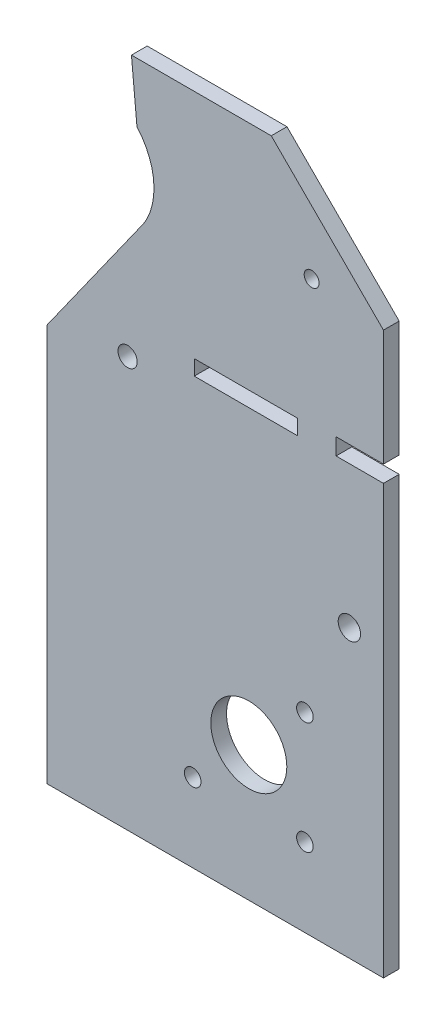
SolidWorks part; units mm, degrees
ref_plane "Front Plane" through (0, 0, 0) normal (0, 0, 1) x (1, 0, 0)
ref_plane "Top Plane" through (0, 0, 0) normal (0, 1, 0) x (1, 0, 0)
ref_plane "Right Plane" through (0, 0, 0) normal (1, 0, 0) x (0, 0, -1)
sketch "Sketch1" plane through (0, 0, 0) normal (0, 0, 1) x (1, 0, 0)
  line L1 (-13.3232, 13.2625) -> (136.6768, 13.2625)
  line L2 (-13.3232, 13.2625) -> (-13.3232, -286.7375)
  line L3 (-13.3232, -286.7375) -> (136.6768, -286.7375)
  line L4 (136.6768, 13.2625) -> (136.6768, -286.7375)
  dimension "D1" = 150
  dimension "D2" = 300
extrude "Boss-Extrude1" add sketch "Sketch1" along normal blind 7
chamfer "Chamfer1" distance 50 angle 45 1 edges at (136.6768, 13.2625, 3.5)
sketch "Sketch2" plane through (0, 0, 7) normal (0, 0, 1) x (1, 0, 0)
  line L0 (136.6768, -286.7375) -> (136.6768, -36.7375) construction
  line L1 (136.6768, -88.4342) -> (115.5612, -88.4342)
  line L2 (136.6768, -88.4342) -> (136.6768, -95.8583)
  line L3 (136.6768, -95.8583) -> (115.5612, -95.8583)
  line L4 (115.5612, -88.4342) -> (115.5612, -95.8583)
  circle A0 centre (104.6726, -32.9544) radius 3.3253
  circle A1 centre (121.5004, -159.1632) radius 4.9921
extrude "Cut-Extrude1" cut sketch "Sketch2" against normal blind 10
sketch "Sketch3" plane through (0, 0, 7) normal (0, 0, 1) x (1, 0, 0)
  circle A0 centre (4.4291, -33.1194) radius 30
  point P2 (4.4291, -33.1194)
extrude "Cut-Extrude2" cut sketch "Sketch3" against normal blind 10
sketch "Sketch4" plane through (0, 0, 7) normal (0, 0, 1) x (1, 0, 0)
  line L0 (-13.3232, -109.8345) -> (30.1354, -48.5851)
  line L1 (-13.3232, 13.2625) -> (-13.3232, -8.9356) construction
  line L2 (30.1354, -48.5851) -> (24.3916, 13.2625)
  line L3 (86.6768, 13.2625) -> (-13.3232, 13.2625) construction
  line L4 (24.3916, 13.2625) -> (-24.5059, 18.0241)
  line L5 (-24.5059, 18.0241) -> (-13.3232, -109.8345)
  circle A0 centre (4.4291, -33.1194) radius 30 construction
  point P10 (24.3916, 13.2625)
extrude "Cut-Extrude3" cut sketch "Sketch4" against normal blind 10
sketch "Sketch5" plane through (0, 0, 7) normal (0, 0, 1) x (1, 0, 0)
  line L0 (-13.3232, -286.7375) -> (136.6768, -286.7375) construction
  line L1 (136.6768, -286.7375) -> (136.6768, -95.8583) construction
  circle A0 centre (76.6768, -226.7375) radius 16.9351
  dimension "D1" = 60
  dimension "D2" = 60
extrude "Cut-Extrude4" cut sketch "Sketch5" against normal blind 10
sketch "Sketch6" plane through (0, 0, 7) normal (0, 0, 1) x (1, 0, 0)
  circle A0 centre (51.6768, -251.7375) radius 3.7055
  circle A1 centre (76.6768, -226.7375) radius 16.9351 construction
  point P6 (0.7359, -162.9577)
  dimension "D1" = 25
  dimension "D2" = 25
extrude "Cut-Extrude5" cut sketch "Sketch6" against normal blind 10
pattern_linear "LPattern1" count 2 spacing 50 along (0, 1, 0) count 2 spacing 50 along (1, 0, 0) skipping (1, 0) of "Cut-Extrude5"
sketch "Sketch7" plane through (0, 0, 7) normal (0, 0, 1) x (1, 0, 0)
  circle A0 centre (22.6781, -103.8953) radius 4.2895
extrude "Cut-Extrude6" cut sketch "Sketch7" against normal blind 10
sketch "Sketch8" plane through (0, 0, 7) normal (0, 0, 1) x (1, 0, 0)
  line L1 (98.4034, -89.8721) -> (52.3743, -89.8721)
  line L2 (98.4034, -89.8721) -> (98.4034, -96.6362)
  line L3 (98.4034, -96.6362) -> (52.3743, -96.6362)
  line L4 (52.3743, -89.8721) -> (52.3743, -96.6362)
extrude "Cut-Extrude7" cut sketch "Sketch8" against normal blind 10
